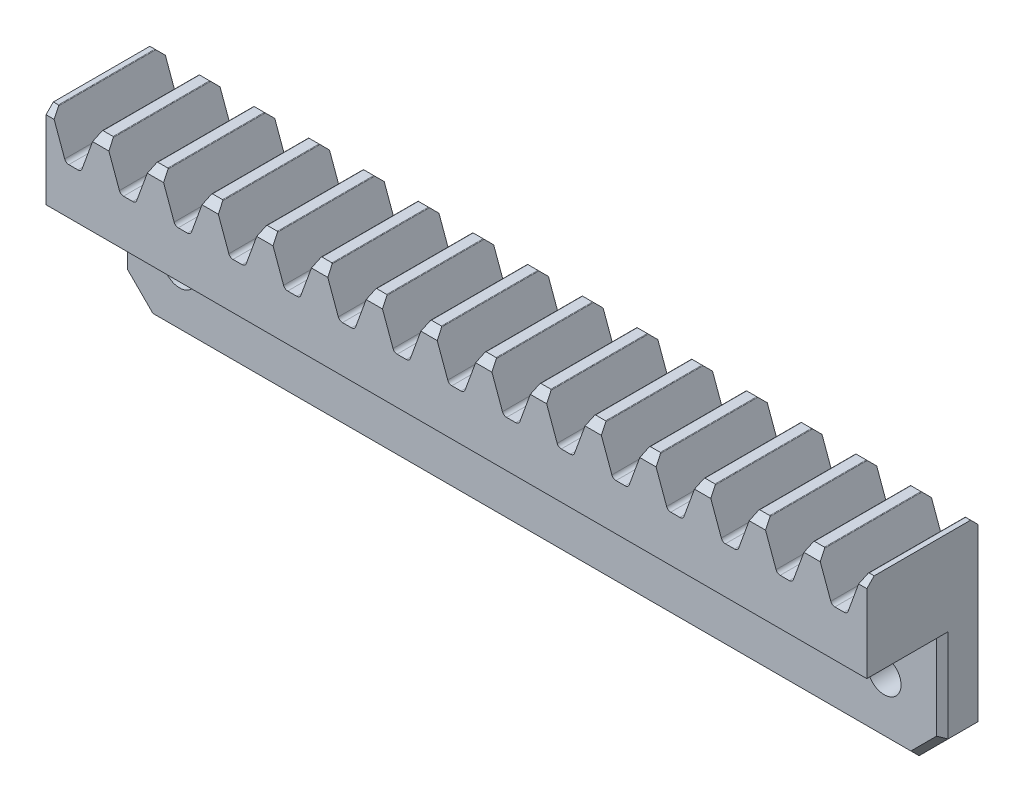
SolidWorks part; units mm, degrees
extrude "Blank" add sketch "BlankSke" against normal blind 19.15
sketch "BlankSke" plane through (0, 0, 0) normal (0, 0, 1) x (1, 0, 0)
  line L1 (0, 0) -> (152, 0)
  line L2 (0, 0) -> (0, 15.7)
  line L3 (0, 15.7) -> (152, 15.7)
  line L4 (152, 0) -> (152, 15.7)
  dimension "Length" = 152
material "PET"
ref_plane "Plane1" through (0, 0, 0) normal (0, 0, 1) x (1, 0, 0)
ref_plane "Plane2" through (0, 0, 0) normal (0, 1, 0) x (1, 0, 0)
ref_plane "Plane3" through (0, 0, 0) normal (1, 0, 0) x (0, 0, -1)
sketch "HoldingSke" plane through (0, 0, 0) normal (0, 1, 0) x (1, 0, 0)
  line L0 (0, 0) -> (0.0464, 0.3301)
  line L1 (-15, 0) -> (100, 0) construction
  line L2 (0, 0) -> (-2.1039, 2.3779)
  line L3 (0, 0) -> (-11.863, 4.5341)
  line L4 (0, 0) -> (8.2133, 2.6687)
  line L5 (0, 0) -> (-23.7986, -8.8762)
  line L6 (0, 0) -> (-10.5278, -7.1032)
  line L9 (-71.009, 38.7566) -> (71.8243, 90.7437)
  line L10 (-76.2, 5.3779) -> (-63.5, 5.3779)
  line L11 (0, 0) -> (-19.15, 0)
  line L12 (-76.2, 101.6) -> (-76.093, 101.6)
  line L13 (24.9733, 27.94) -> (52.9518, 28.4284)
  line L14 (24.9733, 27.94) -> (24.9743, 27.94)
  line L15 (24.9733, 27.94) -> (100.4006, 29.5858)
  circle A0 centre (0, 0) radius 19.05
  circle A1 centre (0, 0) radius 6.35
  circle A2 centre (0, 0) radius 12.7
  dimension "Num_teeth" = 18
  dimension "Width" = 19.15
  dimension "Length" = 152
  dimension "Pitch_height" = 12.7
chamfer "Chamfer1" distance 1.27 angle 45 2 edges at (76, 15.7, 0) (76, 15.7, -19.15)
sketch "TooCutSkeIll" plane through (0, 0, 0) normal (0, 0, 1) x (1, 0, 0)
  line L0 (-3.7404, 15.621) -> (-1.4922, 9.4441)
  line L1 (-0.7865, 8.95) -> (0.7865, 8.95)
  line L2 (1.4922, 9.4441) -> (3.7404, 15.621)
  line L3 (152, 15.7) -> (0, 15.7) construction
  line L4 (0, 0) -> (0, 64.897) construction
  line L5 (-13.208, 12.7) -> (12.954, 12.7) construction
  line L6 (0, 0) -> (152, 0) construction
  line L7 (2.6772, 12.7) -> (2.6772, 48.7463) construction
  line L8 (-2.6772, 12.7) -> (-2.6772, 48.7463) construction
  line L9 (3.8531, 15.7) -> (3.8531, 15.7254)
  line L10 (-3.8531, 15.7) -> (-3.8531, 15.7254)
  line L11 (-3.8531, 15.7254) -> (3.8531, 15.7254)
  arc A0 (0.7865, 8.95) -> (1.4922, 9.4441) centre (0.7865, 9.701) ccw
  arc A1 (-1.4922, 9.4441) -> (-0.7865, 8.95) centre (-0.7865, 9.701) ccw
  arc A2 (3.8531, 15.7) -> (3.7404, 15.621) centre (3.8531, 15.58) ccw
  arc A3 (-3.7404, 15.621) -> (-3.8531, 15.7) centre (-3.8531, 15.58) ccw
  dimension "Addendum_plus" = 3.0254
  dimension "Pitch_height" = 12.7
  dimension "Pressure_angle" = 20
  dimension "Gap_width" = 5.3544
  dimension "Dedendum" = 3.75
extrude "ToothCutIll" cut sketch "TooCutSkeIll" against normal through all
sketch "TooCutSkeSim" plane through (0, 0, 0) normal (0, 0, 1) x (1, 0, 0)
  line L0 (1.3123, 8.95) -> (-1.3123, 8.95)
  line L1 (3.7784, 15.7254) -> (1.3123, 8.95)
  line L2 (0, 17.4625) -> (0, 53.467) construction
  line L3 (3.7784, 15.7254) -> (-3.7784, 15.7254)
  line L6 (-3.7784, 15.7254) -> (-1.3123, 8.95)
  line L9 (-2.6772, 12.7) -> (2.6772, 12.7) construction
  line L10 (0, 0) -> (152, 0) construction
  line L11 (2.6772, 12.7) -> (2.6772, 53.467) construction
  line L12 (-2.6772, 12.7) -> (-2.6772, 53.467) construction
  dimension "Addendum_plus" = 3.0254
  dimension "Pitch_height" = 12.7
  dimension "Pressure_angle" = 20
  dimension "Gap_width" = 5.3544
  dimension "Dedendum" = 3.75
extrude "ToothCutSim" [suppressed] cut sketch "TooCutSkeSim" against normal through all
pattern_linear "TeethCuts" count 17 spacing 9.4248 along (1, 0, 0) of "ToothCutIll", "ToothCutSim"
sketch "Sketch2" plane through (0, 0, 0) normal (-1, 0, 0) x (0, 0, 1)
  line L1 (-19.15, 0) -> (0, 0)
  line L2 (-19.15, 0) -> (-19.15, 15.7)
  line L3 (-19.15, 15.7) -> (0, 15.7)
  line L4 (0, 0) -> (0, 15.7)
extrude "Cut-Extrude1" cut sketch "Sketch2" against normal up to vertex (4.7124 mm away)
sketch "Sketch3" plane through (152, 0, 0) normal (1, 0, 0) x (0, 0, -1)
  line L1 (19.15, 0) -> (0, 0)
  line L2 (19.15, 0) -> (19.15, 15.7)
  line L3 (19.15, 15.7) -> (0, 15.7)
  line L4 (0, 0) -> (0, 15.7)
extrude "Cut-Extrude2" cut sketch "Sketch3" against normal up to vertex (5.9159 mm away)
ref_plane "Plane4" through (0, 12.7, 0) normal (0, -1, 0) x (-1, 0, 0)
hole_wizard "M3 Clearance Slot1" [suppressed] positions "Sketch5" profile "Sketch6" size "M3" standard "ANSI Metric"
sketch "Sketch5" plane through (0, 0, -13) normal (0, 0, -1) x (-1, 0, 0)
  line L0 (-126.0841, 4.475) -> (-136.0841, 4.475) construction
  line L1 (-141.3717, 8.95) -> (-141.3717, 0) construction
  line L2 (-140.5852, 8.95) -> (-142.1581, 8.95) construction
  line L3 (-4.7124, 0) -> (-146.0841, 0) construction
  line L5 (-146.0841, 4.475) -> (-4.7124, 4.475) construction
  line L6 (-146.0841, 0) -> (-146.0841, 14.43) construction
  line L7 (-4.7124, 14.43) -> (-4.7124, 0) construction
  line L8 (-75.3982, 4.475) -> (-75.3982, 0) construction
  point P0 (-131.0841, 4.475)
  point P19 (-141.3717, 4.475)
  point P22 (-75.3982, 4.475)
  point P30 (-19.7124, 4.475)
  dimension "D1" = 10
  dimension "D2" = 10
sketch "Sketch6" plane through (131.0841, 4.475, -13) normal (1, 0, 0) x (0, 1, 0)
  line L0 (0, 0) -> (0, 13)
  line L1 (0, 13) -> (1.7, 13)
  line L2 (1.7, 13) -> (1.7, 0)
  line L5 (1.7, 0) -> (0, 0)
  line L11 (0, -6.35) -> (0, 107.95) construction
  dimension "Thru Hole Dia." = 3.4
  dimension "Thru Hole Depth" = 13
sketch "Sketch7" plane through (0, 0, 0) normal (0, -1, 0) x (1, 0, 0)
  line L0 (4.7124, -19.15) -> (4.7124, 0) construction
  line L1 (146.0841, -19.15) -> (4.7124, -19.15)
  line L2 (146.0841, -19.15) -> (146.0841, -13)
  line L3 (146.0841, -13) -> (4.7124, -13)
  line L4 (4.7124, -19.15) -> (4.7124, -13)
  dimension "D1" = 6.15
extrude "Boss-Extrude1" add sketch "Sketch7" along normal blind 20
hole_wizard "M5 Clearance Hole1" positions "Sketch9" profile "Sketch10" hole size "M5" standard "ANSI Metric" end condition through all
sketch "Sketch9" plane through (0, 0, -13) normal (0, 0, 1) x (1, 0, 0)
  line L0 (146.0841, -10) -> (4.7124, -10) construction
  line L1 (146.0841, -20) -> (146.0841, 0) construction
  line L2 (4.7124, -20) -> (4.7124, 0) construction
  line L3 (75.3982, -10) -> (75.3982, -20) construction
  line L4 (146.0841, -20) -> (4.7124, -20) construction
  point P8 (136.0841, -10)
  point P16 (14.7124, -10)
  dimension "D1" = 10
sketch "Sketch10" plane through (14.7124, -10, -13) normal (1, 0, 0) x (0, -1, 0)
  line L0 (0, 0) -> (0, 6.15)
  line L1 (0, 6.15) -> (2.9, 6.15)
  line L2 (2.9, 6.15) -> (2.9, 0)
  line L5 (2.9, 0) -> (0, 0)
  line L11 (0, -6.35) -> (0, 107.95) construction
  dimension "Thru Hole Dia." = 5.8
  dimension "Thru Hole Depth" = 6.15
chamfer "Chamfer3" distance 5 angle 45 2 edges at (4.7124, -20, -16.075) (146.0841, -20, -16.075)
chamfer "Chamfer2" distance 1 angle 45 8 edges at (75.3982, -20, -13) (146.0841, -7.5, -13) (146.0841, 0, -6.5) (4.7124, -7.5, -13) (4.7124, 0, -6.5) (75.3982, 0, 0) (7.2124, -17.5, -13) (143.5841, -17.5, -13)
equation "' \"Module@HoldingSke\" = 6.35"
equation "' \"Num_teeth@HoldingSke\" = 12"
equation "' \"Ap@HoldingSke\" =  20"
equation "' \"Ap@HoldingSke\" = 20"
equation "' \"Width@HoldingSke\" = 0.25 * 25.4"
equation "' \"Show_teeth@HoldingSke\" = 500"
equation "' \"Backlash@HoldingSke\" = 0.009 * 25.4"
equation "' \"Addendum_fac@HoldingSke\" = 1.0"
equation "' \"Dedendum_fac@HoldingSke\" = 1.25"
equation "' \"Dedendum_add@HoldingSke\" = 0.00005 * 25.4"
equation "' \"Clearance_fac@HoldingSke\" = 0.25"
equation "' \"Pitch_height@HoldingSke\" = 1 * 25.4"
equation "' \"Length@HoldingSke\" = 4.71 * 25.4"
equation "\"Pitch@HoldingSke\" = 1 / \"Module@HoldingSke\""
equation "\"MPH@HoldingSke\" = \"Dedendum_fac@HoldingSke\" / \"Pitch@HoldingSke\" + 2 * \"Dedendum_add@HoldingSke\" + 0.002 * 25.4"
equation "\"MPH@HoldingSke\" = ((sgn( \"MPH@HoldingSke\" - \"Pitch_height@HoldingSke\")+1)*( \"MPH@HoldingSke\" - \"Pitch_height@HoldingSke\"))/2 + \"Pitch_height@HoldingSke\""
equation "\"Blank_height@BlankSke\" = \"Pitch_height@HoldingSke\" + \"Addendum_fac@HoldingSke\"  / \"Pitch@HoldingSke\" "
equation "\"Length@BlankSke\" =  \"Length@HoldingSke\""
equation "\"Face_width@Blank\" = \"Width@HoldingSke\""
equation "\"Pressure_angle@TooCutSkeIll\" = \"Ap@HoldingSke\""
equation "\"Addendum_plus@TooCutSkeIll\" =  \"Addendum_fac@HoldingSke\"  / \"Pitch@HoldingSke\" + 0.001 *25.4"
equation "\"Dedendum@TooCutSkeIll\" = \"Dedendum_fac@HoldingSke\"  / \"Pitch@HoldingSke\""
equation "\"Pitch_height@TooCutSkeIll\" =  \"MPH@HoldingSke\""
equation "\"Gap_width@TooCutSkeIll\" = 3.14159265 / 2 / \"Pitch@HoldingSke\" + 6 * \"Backlash@HoldingSke\""
equation "\"Pressure_angle@TooCutSkeSim\" = \"Ap@HoldingSke\""
equation "\"Addendum_plus@TooCutSkeSim\" =  \"Addendum_fac@HoldingSke\"  / \"Pitch@HoldingSke\" + 0.001 * 25.4"
equation "\"Dedendum@TooCutSkeSim\" = \"Dedendum_fac@HoldingSke\"  / \"Pitch@HoldingSke\""
equation "\"Pitch_height@TooCutSkeSim\" =  \"MPH@HoldingSke\""
equation "\"Gap_width@TooCutSkeSim\" = 3.14159265 / 2 / \"Pitch@HoldingSke\" + 6 * \"Backlash@HoldingSke\""
equation "\"Root_fillet@TooCutSkeIll\" = \"Clearance_fac@HoldingSke\" / \"Pitch@HoldingSke\" + \"Dedendum_add@HoldingSke\""
equation "\"Break_rad@TooCutSkeIll\" = 0.02 / \"Pitch@HoldingSke\" * 2"
equation "\"Linear_pitch@TeethCuts\" = 3.14159265 / \"Pitch@HoldingSke\""
equation "\"Num_teeth@HoldingSke\" = int( ( \"Length@HoldingSke\" + 0 ) / (3.14159265 / \"Pitch@HoldingSke\")) + 0.9999  + 1"
equation " \"Num_teeth@TeethCuts\" = int( \"Show_teeth@HoldingSke\" ) + 1"
equation " \"Num_teeth@TeethCuts\" = ((sgn( \"Num_teeth@TeethCuts\" - \"Num_teeth@HoldingSke\" )-1)*( \"Num_teeth@TeethCuts\" - \"Num_teeth@HoldingSke\" ))/-2+ \"Num_teeth@HoldingSke\""
equation " \"Num_teeth@TeethCuts\" = ((sgn( \"Num_teeth@TeethCuts\" - 2.0)+1)*( \"Num_teeth@TeethCuts\" - 2.0))/2 +2.0"
